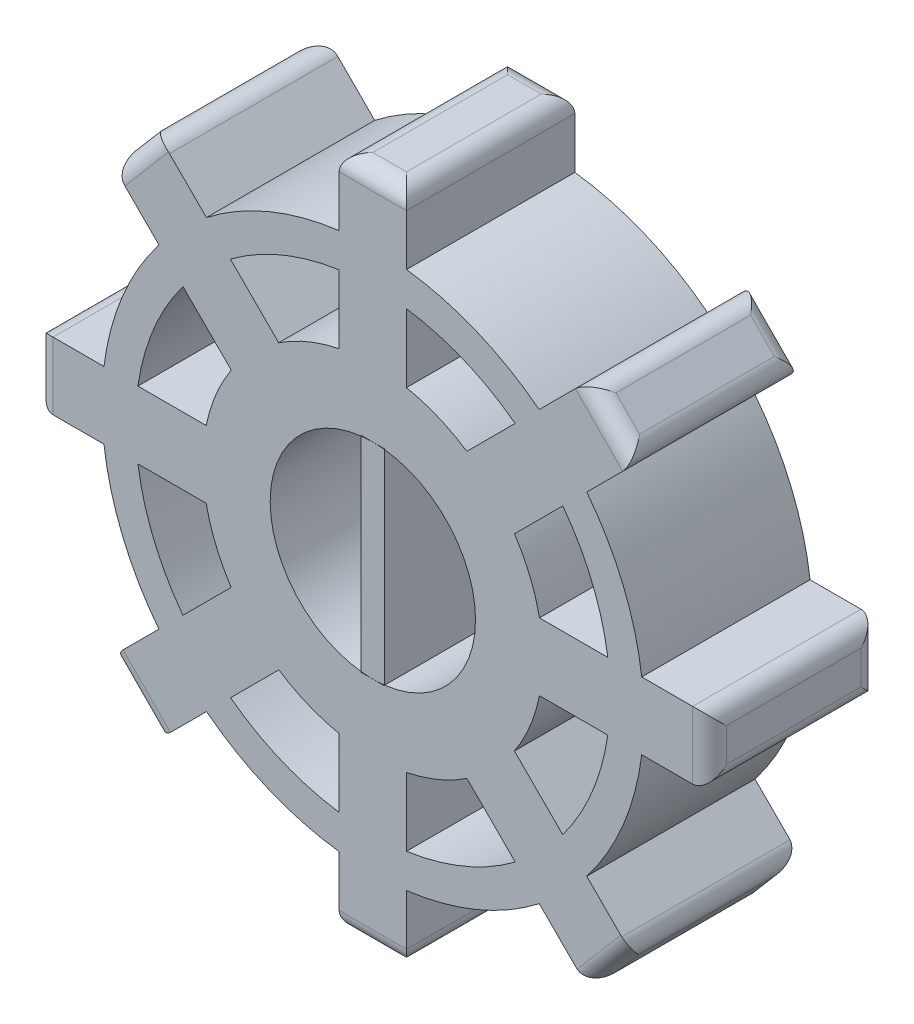
SolidWorks part; units mm, degrees
ref_plane "Front Plane" through (0, 0, 0) normal (0, 0, 1) x (1, 0, 0)
ref_plane "Top Plane" through (0, 0, 0) normal (0, 1, 0) x (1, 0, 0)
ref_plane "Right Plane" through (0, 0, 0) normal (1, 0, 0) x (0, 0, -1)
sketch "Sketch1" plane through (0, 0, 0) normal (0, 0, 1) x (1, 0, 0)
  line L1 (1, -10) -> (-1, -10)
  line L2 (1, -10) -> (1, 10)
  line L3 (1, 10) -> (-1, 10)
  line L4 (-1, -10) -> (-1, 10)
  line L5 (1, -10) -> (-1, 10) construction
  line L6 (1, 10) -> (-1, -10) construction
  line L7 (-10, -1) -> (10, -1)
  line L8 (-10, -1) -> (-10, 1)
  line L9 (-10, 1) -> (10, 1)
  line L10 (10, -1) -> (10, 1)
  line L11 (-10, -1) -> (10, 1) construction
  line L12 (-10, 1) -> (10, -1) construction
  line L13 (-7.7747, -6.3605) -> (-6.3674, -7.7816)
  line L14 (-7.7747, -6.3605) -> (6.3674, 7.7816)
  line L15 (6.3674, 7.7816) -> (7.7747, 6.3605)
  line L16 (-6.3674, -7.7816) -> (7.7747, 6.3605)
  line L17 (-7.7747, -6.3605) -> (7.7747, 6.3605) construction
  line L18 (6.3674, 7.7816) -> (-6.3674, -7.7816) construction
  line L22 (6.4227, -7.8324) -> (7.7194, -6.3097)
  line L23 (6.4227, -7.8324) -> (-7.7194, 6.3097)
  line L24 (-7.7194, 6.3097) -> (-6.4227, 7.8324)
  line L25 (7.7194, -6.3097) -> (-6.4227, 7.8324)
  line L26 (6.4227, -7.8324) -> (-6.4227, 7.8324) construction
  line L27 (-7.7194, 6.3097) -> (7.7194, -6.3097) construction
  line L29 (0.35, -3.05) -> (-0.35, -3.05)
  line L30 (0.35, -3.05) -> (0.35, 3.05)
  line L31 (0.35, 3.05) -> (-0.35, 3.05)
  line L32 (-0.35, -3.05) -> (-0.35, 3.05)
  line L33 (0.35, -3.05) -> (-0.35, 3.05) construction
  line L34 (0.35, 3.05) -> (-0.35, -3.05) construction
  circle A0 centre (0, 0) radius 3.05
  circle A1 centre (0, 0) radius 5.05
  point P20 (0, 0)
  dimension "D1" = 6.1
  dimension "D2" = 2
  dimension "D3" = 45
  dimension "D4" = 2
  dimension "D5" = 135
  dimension "D6" = 20
  dimension "D7" = 0.7
extrude "Boss-Extrude1" add sketch "Sketch1" along normal blind 5 contours A1 L2 L3 L4 | A1 L25 L24 L23 | A1 L16 L15 L14 | A1 L7 L10 L9 | A1 L23 L22 L25 | A1 L4 L1 L2 | A1 L14 L13 L16 | L16 A1 L14 A0 | L14 A1 L2 A0 | L2 A1 L4 A0 | L4 A1 L25 A0 | L25 A1 L23 A0 | L23 A1 L9 A0 | L9 A1 L7 A0 | L7 A1 L14 A0 | L14 A1 L16 A0 | L16 A1 L4 A0 | L2 A1 L23 A0 | L4 A1 L2 A0 | L25 A1 L7 A0 | L23 A1 L25 A0 | L7 A1 L9 A0 | L9 A1 L16 A0 | A1 L9 L8 L7 | L30 A0 L32 L25 L14 | L32 L14 L25 | L25 L30 L14 | L32 L9 L30 L25 L14 | L32 L7 L30 L9 | L32 A0 L30 L23 L16 | L32 L16 L23 | L23 L30 L16 | L32 L23 L16 L30 L7 region at (0, -7.5083, 0) region at (0, -4.0063, 0) region at (1.6319, -3.9354, 0) region at (-1.6307, -3.9367, 0) region at (5.3056, -5.3132, 0) region at (2.8323, -2.8323, 0) region at (-2.8321, -2.8321, 0) region at (-5.3089, -5.3094, 0) region at (0.0003, -2.3116, 0) region at (3.9354, -1.6319, 0) region at (-3.9367, -1.6307, 0) region at (0.2341, -1.4119, 0) region at (7.5083, 0, 0) region at (4.0052, 0, 0) region at (-0.2326, -1.4119, 0) region at (-4.0052, 0, 0) region at (-7.5083, 0, 0) region at (0.0017, -1.14, 0) region at (-3.9354, 1.6319, 0) region at (0, 0, 0) region at (3.9367, 1.6307, 0) region at (-2.8323, 2.8323, 0) region at (-5.3056, 5.3132, 0) region at (-0.0017, 1.14, 0) region at (5.3089, 5.3094, 0) region at (2.8321, 2.8321, 0) region at (-1.6319, 3.9354, 0) region at (0.2326, 1.4119, 0) region at (1.6307, 3.9367, 0) region at (-0.2341, 1.4119, 0) region at (0, 4.0063, 0) region at (0, 7.5083, 0) region at (-0.0003, 2.3116, 0)
fillet "Fillet1" radius 0.5 32 edges at (6.4227, -7.8324, 2.5) (7.0711, -7.0711, 5) (7.7194, -6.3097, 2.5) (7.0711, -7.0711, 0) (10, -1, 2.5) (10, 0, 5) (10, 1, 2.5) (10, 0, 0) (7.7747, 6.3605, 2.5) (7.0711, 7.0711, 5) (6.3674, 7.7816, 2.5) (7.0711, 7.0711, 0) (-6.4227, 7.8324, 2.5) (-7.0711, 7.0711, 5) (-7.7194, 6.3097, 2.5) (-7.0711, 7.0711, 0) (-1, -10, 2.5) (0, -10, 5) (1, -10, 2.5) (0, -10, 0) (-7.7747, -6.3605, 2.5) (-7.0711, -7.0711, 5) (-6.3674, -7.7816, 2.5) (-7.0711, -7.0711, 0) (-10, 1, 2.5) (-10, 0, 5) (-10, -1, 2.5) (-10, 0, 0) (1, 10, 2.5) (0, 10, 5) (-1, 10, 2.5) (0, 10, 0)
sketch "Sketch2" plane through (0, 0, 5) normal (0, 0, 1) x (1, 0, 0)
  circle A0 centre (0, 0) radius 7.05
  circle A1 centre (0, 0) radius 8.05
  arc A2 (-1, 4.95) -> (-2.7958, 4.2055) centre (0, 0) ccw construction
  dimension "D1" = 1
  dimension "D2" = 2
extrude "Boss-Extrude2" add sketch "Sketch2" against normal up to surface (5 mm away) up to face at (0, 0, 0)
